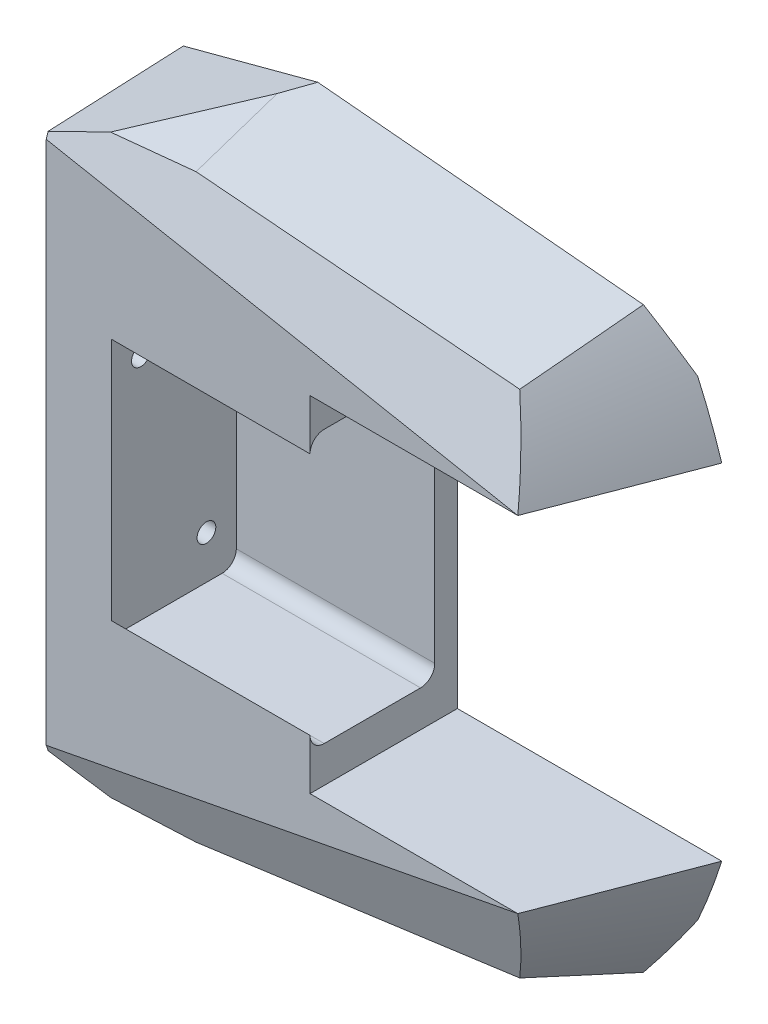
SolidWorks part; units mm, degrees
material "7075-O (SS)"
ref_plane "Top Plane" through (0, 0, 0) normal (0, 0, 1) x (1, 0, 0)
ref_plane "Front Plane" through (0, 0, 0) normal (0, 1, 0) x (1, 0, 0)
ref_plane "Right Plane" through (0, 0, 0) normal (1, 0, 0) x (0, 0, -1)
sketch "Sketch2" plane through (0, 0, 0) normal (0, 0, 1) x (1, 0, 0)
  line L0 (-42.5, 46.6303) -> (-33.7217, 50)
  line L1 (42.5, -50) -> (-42.5, -50)
  line L2 (42.5, -50) -> (42.5, 50)
  line L3 (42.5, 50) -> (-42.5, 50)
  line L4 (-42.5, -50) -> (-42.5, 50)
  line L5 (42.5, -50) -> (-42.5, 50) construction
  line L6 (42.5, 50) -> (-42.5, -50) construction
  line L7 (-17.6637, 50) -> (42.5, 42.6128)
  line L8 (-42.5, 0) -> (42.5, 0) construction
  line L9 (-17.6637, -50) -> (42.5, -42.6128)
  line L10 (-42.5, -46.6303) -> (-33.7217, -50)
  line L11 (42.5, 30.4062) -> (25.8453, 30.4062)
  line L12 (42.5, -30.4062) -> (25.8453, -30.4062)
  line L13 (25.8453, -30.4062) -> (25.8453, 30.4062)
  arc A0 (36.8143, 43.3109) -> (36.8143, -43.3109) centre (-44, 0) cw
  point P0 (0, 0)
  point P19 (42.5, -30.4062)
  point P20 (42.5, 30.4062)
  dimension "D1" = 100
  dimension "D2" = 85
  dimension "D3" = 69
  dimension "D4" = 3.3697
  dimension "D5" = 83
  dimension "D6" = 7.3872
  dimension "D7" = 44
extrude "Body" add sketch "Sketch2" along normal blind 26 contours A0 L12 L13 L11 L7 L3 L0 L4 L10 L1 L9 region at (-6.6242, 0, 0)
sketch "Sketch3" plane through (25.8453, 0, 0) normal (1, 0, 0) x (0, 0, -1)
  line L0 (-26, 30.4062) -> (0, 30.4062) construction
  line L1 (-26, -30.4062) -> (0, -30.4062)
  line L2 (-26, -30.4062) -> (-26, 30.4062)
  line L3 (-26, 30.4062) -> (0, 30.4062)
  line L4 (0, -30.4062) -> (0, 30.4062)
extrude "Center Relief Adjustment" cut sketch "Sketch3" against normal blind 20
draft "Draft around body" type of draft neutral plane draft angle 20 faces to draft 6 face at (-25.6927, 50, 13) face at (9.5753, 46.6555, 13) face at (39.7814, 36.9133, 13) face at (39.7814, -36.9133, 13) face at (-25.6927, -50, 13) face at (9.5753, -46.6555, 13) neutral plane through (0, 0, 26) neutral plane normal (0, 0, 1) parameters "D1"=20
sketch "Sketch5" plane through (-42.5, 0, 0) normal (-1, 0, 0) x (0, 0, 1)
  line L0 (0, -46.6303) -> (0, 46.6303) construction
  line L9 (0, 42) -> (19, 42)
  line L10 (0, 42) -> (0, -42)
  line L11 (0, -42) -> (19, -42)
  line L12 (24, 37) -> (24, -37)
  arc A0 (24, -37) -> (19, -42) centre (19, -37) cw
  arc A1 (24, 37) -> (19, 42) centre (19, 37) ccw
  point P15 (24, -42)
  point P18 (24, 42)
  dimension "D4" = 5
  dimension "D1" = 42
  dimension "D2" = 84
  dimension "D3" = 24
extrude "Face Insert Cut - Front" cut sketch "Sketch5" against normal blind 3
sketch "Sketch6" plane through (0, 0, 0) normal (0, 0, -1) x (-1, 0, 0)
  line L1 (39.5, 42) -> (6.5, 42)
  line L2 (39.5, 42) -> (39.5, -42)
  line L3 (39.5, -42) -> (6.5, -42)
  line L4 (1.5, 37) -> (1.5, -37)
  arc A0 (6.5, -42) -> (1.5, -37) centre (6.5, -37) cw
  arc A1 (6.5, 42) -> (1.5, 37) centre (6.5, 37) ccw
  point P7 (1.5, -42)
  point P10 (1.5, 42)
  dimension "D3" = 5
  dimension "D1" = 38
  dimension "D2" = 84
extrude "Face Insert Cut - Bottom" cut sketch "Sketch6" against normal blind 3
sketch "Sketch7" plane through (0, 0, 3) normal (0, 0, -1) x (-1, 0, 0)
  point P0 (24.45, 29.8957)
  point P3 (24.45, -29.8957)
hole_wizard "M6x1.0 Tapped Hole1" positions "Sketch7" profile "Sketch8" tap size "M6x1.0" standard "ANSI Metric"
sketch "Sketch8" plane through (-24.45, 29.8957, 3) normal (1, 0, 0) x (0, 1, 0)
  line L0 (0, 0) -> (0, 16.5022)
  line L1 (0, 16.5022) -> (2.5, 15)
  line L2 (2.5, 15) -> (2.5, 0)
  line L5 (2.5, 0) -> (0, 0)
  line L10 (0, 16.5022) -> (-2.5, 15) construction
  line L11 (0, -6.35) -> (0, 107.95) construction
  dimension "Tap Drill Dia." = 5
  dimension "Tap Drill Depth" = 15
  dimension "Drill Angle" = 118
cosmetic thread "Hole Thread1" parameters "D1"=12, "D2"=6
cosmetic thread "Hole Thread2" parameters "D1"=12, "D2"=6
sketch "Sketch9" plane through (0, 0, 0) normal (0, 0, -1) x (-1, 0, 0)
  line L0 (42.5, 46.6303) -> (-48.2222, 41.5542)
  line L4 (42.5, 46.6303) -> (18.1671, 64.9129)
  line L5 (18.1671, 64.9129) -> (-44.1118, 53.5746)
  arc A0 (-42.6877, 52.1241) -> (-52.4735, 30.4062) centre (44, 0) ccw construction
  arc A3 (-48.2222, 41.5542) -> (-44.1118, 53.5746) centre (56.438, 12.4787) cw
revolve "Toe side bottom relief" cut sketch "Sketch9" angle 20 about L0
sketch "Sketch11" plane through (0, 0, 0) normal (0, 0, -1) x (-1, 0, 0)
  line L0 (42.5, -46.6303) -> (-48.2222, -41.5542)
  line L1 (42.5, -46.6303) -> (21.2236, -65.429)
  line L2 (21.2236, -65.429) -> (-45.461, -54.5561)
  arc A0 (-52.4735, -30.4062) -> (-42.6877, -52.1241) centre (44, 0) ccw construction
  arc A1 (-45.461, -54.5561) -> (-48.2222, -41.5542) centre (59.1366, -25.5487) cw
revolve "Heel side bottom relief" cut sketch "Sketch11" angle 20 about L0 reverse direction yes
sketch "Sketch13" plane through (0, 0, 26) normal (0, 0, 1) x (1, 0, 0)
  line L0 (-42.5, 46.6303) -> (42.5, 30.4062)
  line L1 (42.5, 30.4062) -> (41.9567, 51.0016)
  line L2 (41.9567, 51.0016) -> (-42.5, 58.9949)
  line L3 (-42.5, 58.9949) -> (-42.5, 46.6303)
revolve "Toe side top relief" cut sketch "Sketch13" angle 20 about L0 reverse direction yes
sketch "Sketch14" plane through (0, 0, 26) normal (0, 0, 1) x (1, 0, 0)
  line L5 (42.5, -30.4062) -> (41.9567, -51.0016)
  line L6 (42.5, -30.4062) -> (-42.5, -46.6303)
  line L7 (-42.5, -46.6303) -> (-42.5, -58.9953)
  line L8 (-42.5, -58.9953) -> (41.9567, -51.0016)
  dimension "D1" = 12.365
revolve "Heel side top relief" cut sketch "Sketch14" angle 20 about L6 reverse direction yes
sketch "Sketch15" plane through (5.8453, 0, 0) normal (1, 0, 0) x (0, 0, -1)
  line L18 (-26, 0) -> (-26, -21.5)
  line L19 (-26, 30.4062) -> (-26, -30.4062) construction
  line L20 (-23.5, -24) -> (-6.5, -24)
  line L21 (-4, -21.5) -> (-4, 21.5)
  line L22 (-6.5, 24) -> (-23.5, 24)
  line L23 (-26, 21.5) -> (-26, 0)
  arc A0 (-6.5, -24) -> (-4, -21.5) centre (-6.5, -21.5) ccw
  arc A1 (-4, 21.5) -> (-6.5, 24) centre (-6.5, 21.5) ccw
  arc A2 (-23.5, 24) -> (-26, 21.5) centre (-23.5, 21.5) ccw
  arc A3 (-26, -21.5) -> (-23.5, -24) centre (-23.5, -21.5) ccw
  point P9 (-4, -24)
  point P14 (-26, 24)
  point P17 (-26, -24)
  dimension "D4" = 2.5
  dimension "D1" = 24
  dimension "D2" = 22
  dimension "D3" = 24
extrude "Shaft block cavity" cut sketch "Sketch15" against normal blind 35
sketch "Sketch16" plane through (-29.1547, 0, 0) normal (1, 0, 0) x (0, 0, -1)
  point P0 (-9.2679, -16.3883)
  point P3 (-20.8321, 16.3883)
hole_wizard "M4x0.7 Tapped Hole1" positions "Sketch16" profile "Sketch17" tap size "M4x0.7" standard "ANSI Metric" end condition through all
sketch "Sketch17" plane through (-29.1547, -16.3883, 9.2679) normal (0, 1, 0) x (0, 0, -1)
  line L0 (0, 0) -> (0, 13.3453)
  line L1 (0, 13.3453) -> (1.65, 13.3453)
  line L2 (1.65, 13.3453) -> (1.65, 0)
  line L5 (1.65, 0) -> (0, 0)
  line L11 (0, -6.35) -> (0, 107.95) construction
  dimension "Thru Tap Drill Dia." = 3.3
  dimension "Thru Tap Drill Depth" = 13.3453
cosmetic thread "Hole Thread3" parameters "D2"=4
cosmetic thread "Hole Thread4" parameters "D2"=4
sketch "Sketch19" plane through (-42.5, 0, 0) normal (-1, 0, 0) x (0, 0, 1)
  line L1 (0, 58.8905) -> (47.5161, 58.8905)
  line L2 (0, 58.8905) -> (0, -58.8905)
  line L3 (0, -58.8905) -> (47.5161, -58.8905)
  line L4 (47.5161, 58.8905) -> (47.5161, -58.8905)
revolve "Face loft for body" cut sketch "Sketch19" angle 4 about L2 reverse direction yes
sketch "Sketch20" plane through (0, 0, 0) normal (0, 0, -1) x (-1, 0, 0)
  line L0 (-50.5124, -36.0429) -> (1.5, -37) construction
  line L2 (-50.5124, 36.0429) -> (1.5, 37) construction
  arc A2 (-52.4735, -30.4062) -> (-48.2222, -41.5542) centre (44, 0) ccw construction
  arc A3 (-48.2222, 41.5542) -> (-52.4735, 30.4062) centre (44, 0) ccw construction
  point P0 (-40.5124, 36.227)
  point P2 (-40.5124, -36.227)
  point P4 (-25.5124, -36.503)
  point P6 (-10.5124, -36.779)
  point P8 (-25.5124, 36.503)
  point P10 (-10.5124, 36.779)
  dimension "D1" = 10
  dimension "D2" = 15
  dimension "D3" = 15
  dimension "D4" = 10
  dimension "D5" = 15
  dimension "D6" = 15
hole_wizard "M5x0.8 Tapped Hole1" positions "Sketch20" profile "Sketch21" tap size "M5x0.8" standard "ANSI Metric"
sketch "Sketch21" plane through (40.5124, 36.227, 0) normal (1, 0, 0) x (0, 1, 0)
  line L0 (0, 0) -> (0, 17.2618)
  line L1 (0, 17.2618) -> (2.1, 16)
  line L2 (2.1, 16) -> (2.1, 3.15)
  line L3 (2.1, 3.15) -> (5.25, 0)
  line L5 (5.25, 0) -> (0, 0)
  line L6 (-2.1, 3.15) -> (-5.25, 0) construction
  line L10 (0, 17.2618) -> (-2.1, 16) construction
  line L11 (0, -6.35) -> (0, 107.95) construction
  dimension "Tap Drill Dia." = 4.2
  dimension "Tap Drill Depth" = 16
  dimension "Near C'Sink Dia." = 10.5
  dimension "Near C'Sink Angle" = 90
  dimension "Drill Angle" = 118
cosmetic thread "Hole Thread5" parameters "D1"=10, "D2"=5
cosmetic thread "Hole Thread6" parameters "D1"=10, "D2"=5
cosmetic thread "Hole Thread7" parameters "D1"=10, "D2"=5
cosmetic thread "Hole Thread8" parameters "D1"=10, "D2"=5
cosmetic thread "Hole Thread9" parameters "D1"=10, "D2"=5
cosmetic thread "Hole Thread10" parameters "D1"=10, "D2"=5
